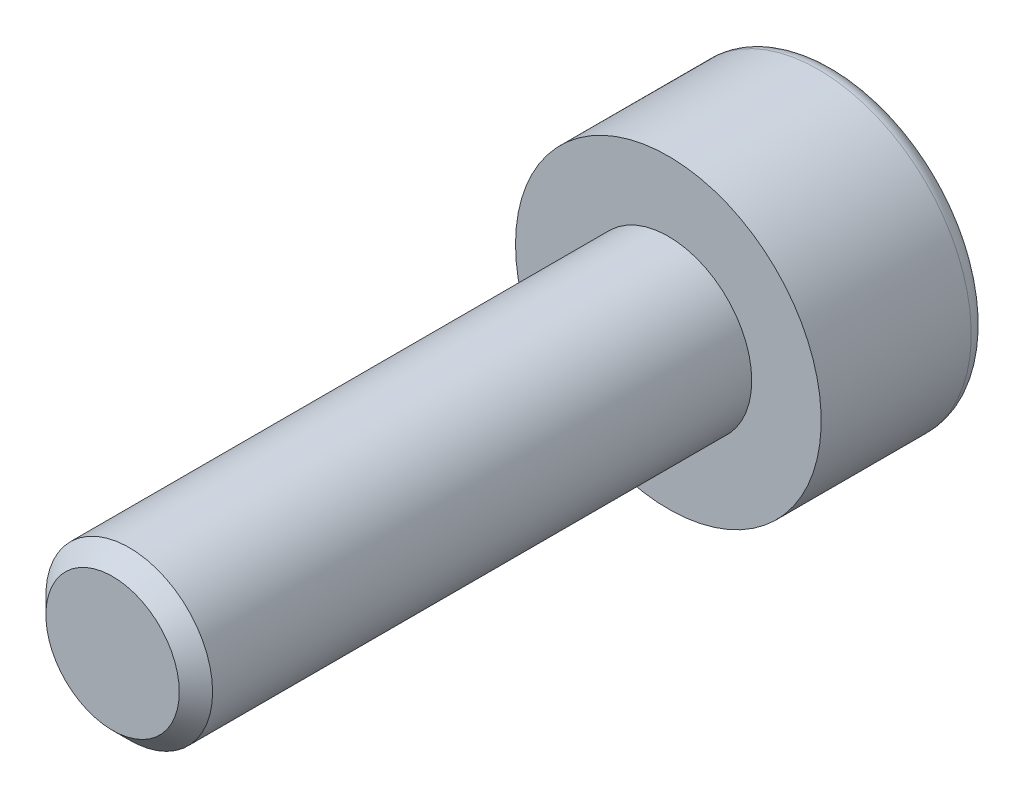
SolidWorks part; units mm, degrees
ref_plane "Plan1" through (0, 0, 0) normal (0, 0, 1) x (1, 0, 0)
ref_plane "Plan2" through (0, 0, 0) normal (0, 1, 0) x (1, 0, 0)
ref_plane "Plan3" through (0, 0, 0) normal (1, 0, 0) x (0, 0, -1)
ref_axis "Z Axis" through (0, 0, -50) along (0, 0, 1)
sketch "Esquisse1" plane through (0, 0, 0) normal (0, 1, 0) x (1, 0, 0)
  line L0 (0, 0) -> (0, 3) construction
  line L1 (0, 0) -> (2.75, 0)
  line L2 (0, 0) -> (0, 3)
  line L3 (0, 3) -> (2.45, 3)
  line L5 (2.75, 0) -> (2.75, 2.7)
  arc A0 (2.45, 3) -> (2.75, 2.7) centre (2.45, 2.7) cw
  dimension "D3" = 0.3
  dimension "D1" = 2.75
  dimension "D2" = 3
revolve "Base-Révolution" add sketch "Esquisse1" angle 360 about L0 reverse direction yes
sketch "Esquisse2" plane through (0, 0, -3) normal (0, 0, 1) x (1, 0, 0)
  line L0 (1.5, -0.866) -> (1.5, 0.866)
  line L1 (0, 0) -> (1.5, 0.866) construction
  line L2 (1, 0) -> (1.5, 0) construction
  line L3 (0, 1.7321) -> (1.5, 0.866)
  line L4 (0, -1.7321) -> (1.5, -0.866)
  line L5 (0, 0) -> (0, 1.5) construction
  line L6 (-1.5, -0.866) -> (-1.5, 0.866)
  line L7 (0, 1.7321) -> (-1.5, 0.866)
  line L8 (0, -1.7321) -> (-1.5, -0.866)
  circle A0 centre (0, 0) radius 1.5 construction
  dimension "D2" = 30
  dimension "D1" = 3
extrude "enlev-mat-Extru1" cut sketch "Esquisse2" along normal blind 2
sketch "Esquisse3" plane through (0, 0, 0) normal (0, 1, 0) x (1, 0, 0)
  line L1 (0, 0) -> (0, -10) construction
  line L2 (0, 0) -> (1.5, 0)
  line L3 (0, 0) -> (0, -10)
  line L4 (0, -10) -> (1.5, -10)
  line L6 (1.5, 0) -> (1.5, -10)
  dimension "D1" = 10
  dimension "D2" = 1.5
revolve "Boss.-Révol.1" add sketch "Esquisse3"
cosmetic thread "Représentation de filetage1"
chamfer "Chanfrein1" distance 0.3 angle 45 1 edges at (1.5, 0, 10)
sketch "Esquisse4" plane through (0, 0, 0) normal (0, 1, 0) x (1, 0, 0)
  line L0 (1.073, -10.0427) -> (1.073, -9.9573)
  line L1 (-1.5, -10) -> (1.5, -10) construction
  line L2 (1.073, -9.9573) -> (1.5427, -9.6861)
  line L3 (1.073, -10.0427) -> (1.5427, -10.3139)
  line L4 (1.5427, -9.6861) -> (1.5427, -10.3139)
  line L5 (1.5, -10) -> (1.5, 0) construction
  point P4 (1.5, -10)
  dimension "D2" = 0.0427
  dimension "D3" = 0.0427
  dimension "D4" = 0.4697
  dimension "D5" = 60
  dimension "D1" = 0.427
  dimension "D6" = 60
sketch "Esquisse5" plane through (0, 0, 10) normal (0, 0, 1) x (1, 0, 0)
  circle A0 centre (0, 0) radius 1.5 construction
  circle A1 centre (0, 0) radius 1.5
curve "Hélice1" pitch 0.7 height 14 turns 20
sweep "Enlèvement de matière-Balayage1" [suppressed] cut profiles "Esquisse4" path "Hélice1"
equation "\"D3@Esquisse1\"=\"D2@Esquisse1\"/10"
equation "\"D1@Chanfrein1\"=\"D2@Esquisse3\"*0.2"
equation "\"D3@Esquisse4\"=0.1*\"D1@Esquisse4\""
equation "\"D4@Esquisse4\"=1.1*\"D1@Esquisse4\""
equation "\"D2@Esquisse4\"=0.1*\"D1@Esquisse4\""
equation "\"D1@Esquisse4\"=0.61*\"D4@Hélice1\""
